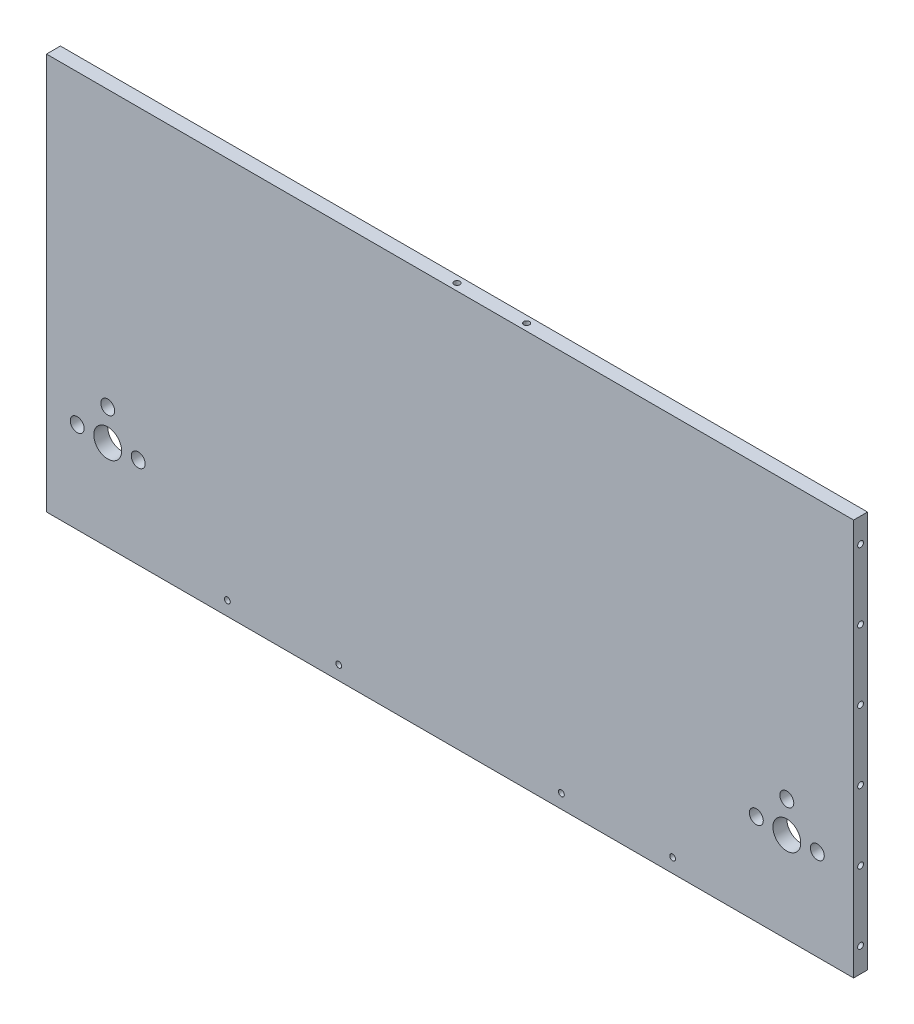
SolidWorks part; units mm, degrees
material "1.4511 (X3CrNb17)"
ref_plane "前视基准面" through (0, 0, 0) normal (0, 0, 1) x (1, 0, 0)
ref_plane "上视基准面" through (0, 0, 0) normal (0, 1, 0) x (1, 0, 0)
ref_plane "右视基准面" through (0, 0, 0) normal (1, 0, 0) x (0, 0, -1)
sketch "草图1" plane through (0, 0, 0) normal (0, 0, 1) x (1, 0, 0)
  line L1 (-290, 142.5) -> (290, 142.5)
  line L2 (-290, 142.5) -> (-290, -142.5)
  line L3 (-290, -142.5) -> (290, -142.5)
  line L4 (290, 142.5) -> (290, -142.5)
  line L5 (-290, 142.5) -> (290, -142.5) construction
  line L6 (-290, -142.5) -> (290, 142.5) construction
  point P0 (0, 0)
  dimension "D1" = 580
  dimension "D2" = 285
extrude "凸台-拉伸1" add sketch "草图1" along normal blind 10
sketch "草图3" plane through (-290, 0, 0) normal (-1, 0, 0) x (0, 0, 1)
  line L0 (10, 142.5) -> (0, 142.5) construction
  point P0 (5, 125)
  point P4 (5, 75)
  point P5 (5, 25)
  point P6 (5, -25)
  point P7 (5, -75)
  point P8 (5, -125)
  dimension "D1" = 17.5
  dimension "D2" = 6
hole_wizard "M5 螺纹孔1" positions "草图4" profile "草图5" tap size "M5" standard "GB"
sketch "草图4" plane through (-290, 0, 0) normal (-1, 0, 0) x (0, 0, 1)
  point P0 (5, 125)
  point P3 (5, 75)
  point P6 (5, 25)
  point P9 (5, -25)
  point P12 (5, -75)
  point P15 (5, -125)
sketch "草图5" plane through (-290, 125, 5) normal (0, 1, 0) x (0, 0, 1)
  line L0 (0, 0) -> (0, 15.2618)
  line L1 (0, 15.2618) -> (2.1, 14)
  line L2 (2.1, 14) -> (2.1, 0)
  line L5 (2.1, 0) -> (0, 0)
  line L10 (0, 15.2618) -> (-2.1, 14) construction
  line L11 (0, -6.35) -> (0, 107.95) construction
  dimension "螺纹孔钻头直径" = 4.2
  dimension "螺纹孔钻头深度" = 14
  dimension "导头角度" = 118
cosmetic thread "孔螺蚊线1" parameters "D1"=10, "D2"=5
cosmetic thread "孔螺蚊线2" parameters "D1"=10, "D2"=5
cosmetic thread "孔螺蚊线3" parameters "D1"=10, "D2"=5
cosmetic thread "孔螺蚊线4" parameters "D1"=10, "D2"=5
cosmetic thread "孔螺蚊线5" parameters "D1"=10, "D2"=5
cosmetic thread "孔螺蚊线6" parameters "D1"=10, "D2"=5
mirror "镜向1" about plane through (0, 0, 0) normal (1, 0, 0) of "M5 螺纹孔1"
cosmetic thread "孔螺蚊线7" parameters "D1"=10, "D2"=5
cosmetic thread "孔螺蚊线8" parameters "D1"=10, "D2"=5
cosmetic thread "孔螺蚊线9" parameters "D1"=10, "D2"=5
cosmetic thread "孔螺蚊线10" parameters "D1"=10, "D2"=5
cosmetic thread "孔螺蚊线11" parameters "D1"=10, "D2"=5
cosmetic thread "孔螺蚊线12" parameters "D1"=10, "D2"=5
sketch "草图6" plane through (0, -142.5, 0) normal (0, -1, 0) x (1, 0, 0)
  line L0 (-290, 10) -> (-290, 0) construction
  point P0 (0, 5)
  point P5 (50, 5)
  dimension "D1" = 290
  dimension "D2" = 2
hole_wizard "M5 螺纹孔2" positions "草图7" profile "草图8" tap size "M5" standard "GB" end condition through all
sketch "草图7" plane through (0, -142.5, 0) normal (0, -1, 0) x (-1, 0, 0)
  point P0 (0, -5)
  point P3 (-50, -5)
sketch "草图8" plane through (0, -142.5, 5) normal (1, 0, 0) x (0, 0, -1)
  line L0 (0, 0) -> (0, 285)
  line L1 (0, 285) -> (2.1, 285)
  line L2 (2.1, 285) -> (2.1, 0)
  line L5 (2.1, 0) -> (0, 0)
  line L11 (0, -6.35) -> (0, 107.95) construction
  dimension "通孔螺纹孔钻头直径" = 4.2
  dimension "通孔螺纹孔钻头深度" = 285
cosmetic thread "孔螺蚊线13" parameters "D2"=5
cosmetic thread "孔螺蚊线14" parameters "D2"=5
sketch "草图9" plane through (0, 0, 10) normal (0, 0, 1) x (1, 0, 0)
  line L0 (-160, -132.5) -> (160, -132.5) construction
  line L1 (0, 0) -> (0, -142.5) construction
  line L2 (-290, -142.5) -> (290, -142.5) construction
  line L3 (-80, -132.5) -> (80, -132.5) construction
  point P7 (0, -132.5)
  point P10 (0, -132.5)
  dimension "D1" = 10
  dimension "D2" = 320
  dimension "D3" = 160
  dimension "D4" = 10
hole_wizard "M5 螺纹孔3" positions "草图10" profile "草图11" tap size "M5" standard "GB" end condition through all
sketch "草图10" plane through (0, 0, 10) normal (0, 0, 1) x (1, 0, 0)
  point P0 (-160, -132.5)
  point P3 (-80, -132.5)
  point P6 (80, -132.5)
  point P9 (160, -132.5)
sketch "草图11" plane through (-160, -132.5, 10) normal (1, 0, 0) x (0, -1, 0)
  line L0 (0, 0) -> (0, 10)
  line L1 (0, 10) -> (2.1, 10)
  line L2 (2.1, 10) -> (2.1, 0)
  line L5 (2.1, 0) -> (0, 0)
  line L11 (0, -6.35) -> (0, 107.95) construction
  dimension "通孔螺纹孔钻头直径" = 4.2
  dimension "通孔螺纹孔钻头深度" = 10
cosmetic thread "孔螺蚊线15" parameters "D2"=5
cosmetic thread "孔螺蚊线16" parameters "D2"=5
cosmetic thread "孔螺蚊线17" parameters "D2"=5
cosmetic thread "孔螺蚊线18" parameters "D2"=5
sketch "草图12" plane through (0, 0, 10) normal (0, 0, 1) x (1, 0, 0)
  line L0 (-267.92, -77.07) -> (-224.08, -77.07) construction
  line L1 (-290, -142.5) -> (290, -142.5) construction
  line L2 (-290, 142.5) -> (-290, -142.5) construction
  line L3 (-246, -55.15) -> (-246, -77.5) construction
  circle A0 centre (-246, -55.15) radius 5
  circle A1 centre (-267.92, -77.07) radius 5
  circle A2 centre (-224.08, -77.07) radius 5
  circle A3 centre (-246, -77.5) radius 10
  point P6 (-246, -55.15)
  dimension "D6" = 10
  dimension "D7" = 10
  dimension "D8" = 10
  dimension "D10" = 20
  dimension "D1" = 43.84
  dimension "D2" = 65.43
  dimension "D3" = 22.08
  dimension "D4" = 44
  dimension "D5" = 87.35
  dimension "D9" = 22.35
extrude "切除-拉伸1" cut sketch "草图12" against normal through all contours A1 | A2 | A0
ref_plane "基准面1" through (-2, 0, 0) normal (1, 0, 0) x (0, 0, -1)
mirror "镜向2" about plane through (-2, 0, 0) normal (1, 0, 0) of "切除-拉伸1"
extrude "切除-拉伸2" cut sketch "草图12<4>" against normal through all contours A3
sketch "草图12<4>" plane through (0, 0, 10) normal (0, 0, 1) x (1, 0, 0) same geometry as "草图12"
mirror "镜向3" about plane through (-2, 0, 0) normal (1, 0, 0) of "切除-拉伸2"
